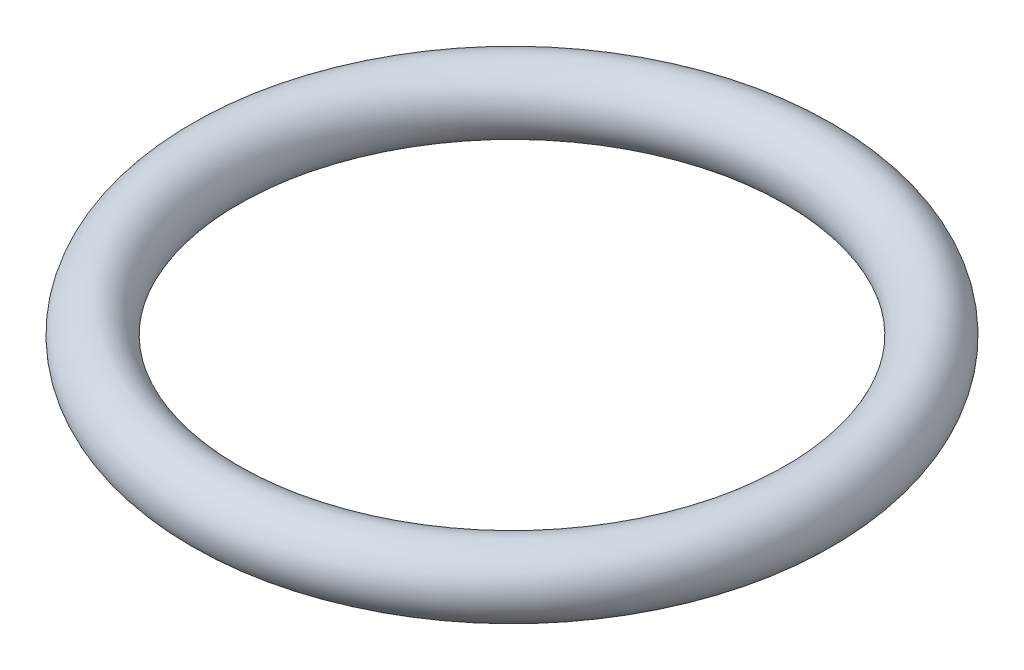
SolidWorks part; units mm, degrees
ref_plane "Front Plane" through (0, 0, 0) normal (0, 0, 1) x (1, 0, 0)
ref_plane "Top Plane" through (0, 0, 0) normal (0, 1, 0) x (1, 0, 0)
ref_plane "Right Plane" through (0, 0, 0) normal (1, 0, 0) x (0, 0, -1)
sketch "Sketch3" plane through (0, 0, 0) normal (0, 1, 0) x (1, 0, 0)
  circle A0 centre (0, 0) radius 22.5
  dimension "D1" = 45
sweep "Sweep1" add path "Sketch3" circular profile diameter 5 parameters "D3"=5
